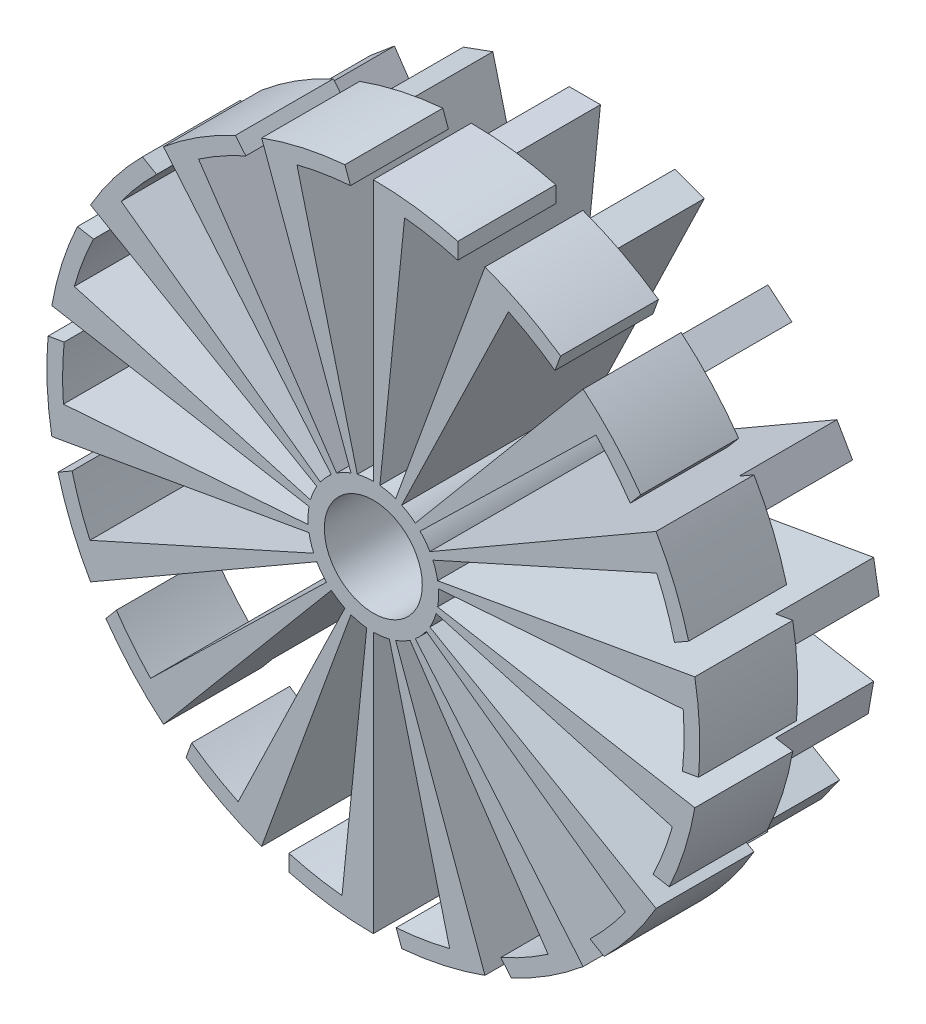
SolidWorks part; units mm, degrees
note: The reader was unsure of these and kept them because the rebuilt part matched: shared geometry of "Schizzo1<12>", "Schizzo1<13>", "Schizzo1<14>", "Schizzo1<16>", "Schizzo1<17>".
ref_plane "Piano frontale" through (0, 0, 0) normal (0, 0, 1) x (1, 0, 0)
ref_plane "Piano superiore" through (0, 0, 0) normal (0, 1, 0) x (1, 0, 0)
ref_plane "Piano destro" through (0, 0, 0) normal (1, 0, 0) x (0, 0, -1)
sketch "Schizzo1" plane through (0, 0, 0) normal (0, 0, 1) x (1, 0, 0)
  line L0 (0, 20) -> (0, 100)
  line L1 (25.8819, 96.5926) -> (25.8819, 91.5926)
  line L2 (9.5838, 94.6954) -> (2.0138, 19.8984)
  line L3 (6.8404, 18.7939) -> (34.202, 93.9693)
  line L4 (57.3576, 81.9152) -> (55.6475, 77.2167)
  line L5 (41.3936, 85.7067) -> (8.698, 18.0096)
  line L6 (12.8558, 15.3209) -> (64.2788, 76.6044)
  line L7 (81.9152, 57.3576) -> (78.7013, 53.5274)
  line L8 (68.2107, 66.3806) -> (14.3331, 13.9485)
  line L9 (17.3205, 10) -> (86.6025, 50)
  line L10 (96.5926, 25.8819) -> (92.2625, 23.3819)
  line L11 (86.8006, 39.0479) -> (18.2394, 8.2051)
  line L12 (19.6962, 3.473) -> (98.4808, 17.3648)
  line L13 (99.6195, -8.7156) -> (94.6954, -9.5838)
  line L14 (94.921, 7.0055) -> (19.9458, 1.4721)
  line L15 (19.6962, -3.473) -> (98.4808, -17.3648)
  line L16 (90.6308, -42.2618) -> (85.7067, -41.3936)
  line L17 (91.5926, -25.8819) -> (19.2464, -5.4386)
  line L18 (17.3205, -10) -> (86.6025, -50)
  line L19 (70.7107, -70.7107) -> (66.3806, -68.2107)
  line L20 (77.2167, -55.6475) -> (16.2256, -11.6932)
  line L21 (12.8558, -15.3209) -> (64.2788, -76.6044)
  line L22 (42.2618, -90.6308) -> (39.0479, -86.8006)
  line L23 (53.5274, -78.7013) -> (11.2477, -16.5375)
  line L24 (6.8404, -18.7939) -> (34.202, -93.9693)
  line L25 (8.7156, -99.6195) -> (7.0055, -94.921)
  line L26 (23.3819, -92.2625) -> (4.9132, -19.3871)
  line L27 (0, -20) -> (0, -100)
  line L28 (-25.8819, -96.5926) -> (-25.8819, -91.5926)
  line L29 (-9.5838, -94.6954) -> (-2.0138, -19.8984)
  line L30 (-6.8404, -18.7939) -> (-34.202, -93.9693)
  line L31 (-57.3576, -81.9152) -> (-55.6475, -77.2167)
  line L32 (-41.3936, -85.7067) -> (-8.698, -18.0096)
  line L33 (-12.8558, -15.3209) -> (-64.2788, -76.6044)
  line L34 (-81.9152, -57.3576) -> (-78.7013, -53.5274)
  line L35 (-68.2107, -66.3806) -> (-14.3331, -13.9485)
  line L36 (-17.3205, -10) -> (-86.6025, -50)
  line L37 (-96.5926, -25.8819) -> (-92.2625, -23.3819)
  line L38 (-86.8006, -39.0479) -> (-18.2394, -8.2051)
  line L39 (-19.6962, -3.473) -> (-98.4808, -17.3648)
  line L40 (-99.6195, 8.7156) -> (-94.6954, 9.5838)
  line L41 (-94.921, -7.0055) -> (-19.9458, -1.4721)
  line L42 (-19.6962, 3.473) -> (-98.4808, 17.3648)
  line L43 (-90.6308, 42.2618) -> (-85.7067, 41.3936)
  line L44 (-91.5926, 25.8819) -> (-19.2464, 5.4386)
  line L45 (-17.3205, 10) -> (-86.6025, 50)
  line L46 (-70.7107, 70.7107) -> (-66.3806, 68.2107)
  line L47 (9.5838, 94.6954) -> (0, 94.6954)
  line L48 (-12.8558, 15.3209) -> (-64.2788, 76.6044)
  line L49 (-42.2618, 90.6308) -> (-39.0479, 86.8006)
  line L50 (-53.5274, 78.7013) -> (-11.2477, 16.5375)
  line L51 (-6.8404, 18.7939) -> (-34.202, 93.9693)
  line L52 (-8.7156, 99.6195) -> (-7.0055, 94.921)
  line L53 (-23.3819, 92.2625) -> (-4.9132, 19.3871)
  line L54 (-77.2167, 55.6475) -> (-16.2256, 11.6932)
  line L55 (-23.3819, 92.2625) -> (-32.3877, 88.9846)
  line L56 (-53.5274, 78.7013) -> (-60.869, 72.5409)
  line L57 (-77.2167, 55.6475) -> (-16.2256, 11.6932) [skipped]
  line L58 (-77.2167, 55.6475) -> (-82.0086, 47.3477)
  line L59 (-91.5926, 25.8819) -> (-93.2568, 16.4437)
  line L60 (-94.921, -7.0055) -> (-93.2568, -16.4437)
  line L61 (-86.8006, -39.0479) -> (-82.0086, -47.3477)
  line L62 (-68.2107, -66.3806) -> (-60.869, -72.5409)
  line L63 (-41.3936, -85.7067) -> (-32.3877, -88.9846)
  line L64 (-9.5838, -94.6954) -> (0, -94.6954)
  line L65 (23.3819, -92.2625) -> (32.3877, -88.9846)
  line L66 (41.3936, 85.7067) -> (32.3877, 88.9846)
  line L67 (68.2107, 66.3806) -> (60.869, 72.5409)
  line L68 (86.8006, 39.0479) -> (82.0086, 47.3477)
  line L69 (94.921, 7.0055) -> (93.2568, 16.4437)
  line L70 (91.5926, -25.8819) -> (93.2568, -16.4437)
  line L71 (77.2167, -55.6475) -> (82.8486, -47.8327)
  line L72 (53.5274, -78.7013) -> (60.869, -72.5409)
  circle A0 centre (0, 0) radius 20
  arc A1 (0, 100) -> (25.8819, 96.5926) centre (0, 0) cw
  arc A2 (25.8819, 91.5926) -> (9.5838, 94.6954) centre (0, 0) ccw
  arc A3 (34.202, 93.9693) -> (57.3576, 81.9152) centre (0, 0) cw
  arc A4 (55.6475, 77.2167) -> (41.3936, 85.7067) centre (0, 0) ccw
  arc A5 (64.2788, 76.6044) -> (81.9152, 57.3576) centre (0, 0) cw
  arc A6 (78.7013, 53.5274) -> (68.2107, 66.3806) centre (0, 0) ccw
  arc A7 (86.6025, 50) -> (96.5926, 25.8819) centre (0, 0) cw
  arc A8 (92.2625, 23.3819) -> (86.8006, 39.0479) centre (0, 0) ccw
  arc A9 (98.4808, 17.3648) -> (99.6195, -8.7156) centre (0, 0) cw
  arc A10 (94.6954, -9.5838) -> (94.921, 7.0055) centre (0, 0) ccw
  arc A11 (98.4808, -17.3648) -> (90.6308, -42.2618) centre (0, 0) cw
  arc A12 (85.7067, -41.3936) -> (91.5926, -25.8819) centre (0, 0) ccw
  arc A13 (86.6025, -50) -> (70.7107, -70.7107) centre (0, 0) cw
  arc A14 (66.3806, -68.2107) -> (77.2167, -55.6475) centre (0, 0) ccw
  arc A15 (64.2788, -76.6044) -> (42.2618, -90.6308) centre (0, 0) cw
  arc A16 (39.0479, -86.8006) -> (53.5274, -78.7013) centre (0, 0) ccw
  arc A17 (34.202, -93.9693) -> (8.7156, -99.6195) centre (0, 0) cw
  arc A18 (7.0055, -94.921) -> (23.3819, -92.2625) centre (0, 0) ccw
  arc A19 (0, -100) -> (-25.8819, -96.5926) centre (0, 0) cw
  arc A20 (-25.8819, -91.5926) -> (-9.5838, -94.6954) centre (0, 0) ccw
  arc A21 (-34.202, -93.9693) -> (-57.3576, -81.9152) centre (0, 0) cw
  arc A22 (-55.6475, -77.2167) -> (-41.3936, -85.7067) centre (0, 0) ccw
  arc A23 (-64.2788, -76.6044) -> (-81.9152, -57.3576) centre (0, 0) cw
  arc A24 (-78.7013, -53.5274) -> (-68.2107, -66.3806) centre (0, 0) ccw
  arc A25 (-86.6025, -50) -> (-96.5926, -25.8819) centre (0, 0) cw
  arc A26 (-92.2625, -23.3819) -> (-86.8006, -39.0479) centre (0, 0) ccw
  arc A27 (-98.4808, -17.3648) -> (-99.6195, 8.7156) centre (0, 0) cw
  arc A28 (-94.6954, 9.5838) -> (-94.921, -7.0055) centre (0, 0) ccw
  arc A29 (-98.4808, 17.3648) -> (-90.6308, 42.2618) centre (0, 0) cw
  arc A30 (-85.7067, 41.3936) -> (-91.5926, 25.8819) centre (0, 0) ccw
  arc A31 (-86.6025, 50) -> (-70.7107, 70.7107) centre (0, 0) cw
  arc A32 (-66.3806, 68.2107) -> (-77.2167, 55.6475) centre (0, 0) ccw
  arc A33 (-64.2788, 76.6044) -> (-42.2618, 90.6308) centre (0, 0) cw
  arc A34 (-39.0479, 86.8006) -> (-53.5274, 78.7013) centre (0, 0) ccw
  arc A35 (-34.202, 93.9693) -> (-8.7156, 99.6195) centre (0, 0) cw
  arc A36 (-7.0055, 94.921) -> (-23.3819, 92.2625) centre (0, 0) ccw
  circle A37 centre (0, 0) radius 15
  circle A38 centre (0, 0) radius 5
  point P113 (0, 0)
  point P189 (0, 0)
  dimension "D1" = 18
  dimension "D2" = 80
  dimension "D3" = 100
  dimension "D4" = 10
  dimension "D5" = 40
extrude "Estrusione-Estrusione1" add sketch "Schizzo1" along normal blind 30
extrude "Estrusione-Estrusione8" add sketch "Schizzo1<12>" against normal blind 30 separate body contours A37
sketch "Schizzo1<12>" plane through (0, 0, 0) normal (0, 0, 1) x (1, 0, 0) same geometry as "Schizzo1"
extrude "Estrusione-Estrusione9" add sketch "Schizzo1<13>" against normal blind 30 separate body
sketch "Schizzo1<13>" plane through (0, 0, 0) normal (0, 0, 1) x (1, 0, 0) same geometry as "Schizzo1"
extrude "Estrusione-Estrusione10" add sketch "Schizzo1<14>" against normal blind 30
sketch "Schizzo1<14>" plane through (0, 0, 0) normal (0, 0, 1) x (1, 0, 0) same geometry as "Schizzo1"
extrude "Estrusione-Estrusione11" add sketch "Schizzo1<16>" along normal blind 30
sketch "Schizzo1<16>" plane through (0, 0, 0) normal (0, 0, 1) x (1, 0, 0) same geometry as "Schizzo1"
extrude "Estrusione-Estrusione12" add sketch "Schizzo1<17>" along normal blind 30 contours A0 L53 L55 L51 | A0 L2 L47 L0 | A0 L5 L66 L3 | A0 L8 L67 L6 | A0 L11 L68 L9 | A0 L14 L69 L12 | A0 L17 L70 L15 | A0 L20 L71 L18 | A0 L23 L72 L21 | A0 L26 L65 L24 | A0 L29 L64 L27 | A0 L32 L63 L30 | A0 L35 L62 L33 | A0 L38 L61 L36 | A0 L41 L60 L39 | A0 L44 L59 L42 | A0 L54 L58 L45 | A0 L50 L56 L48
sketch "Schizzo1<17>" plane through (0, 0, 0) normal (0, 0, 1) x (1, 0, 0) same geometry as "Schizzo1"
